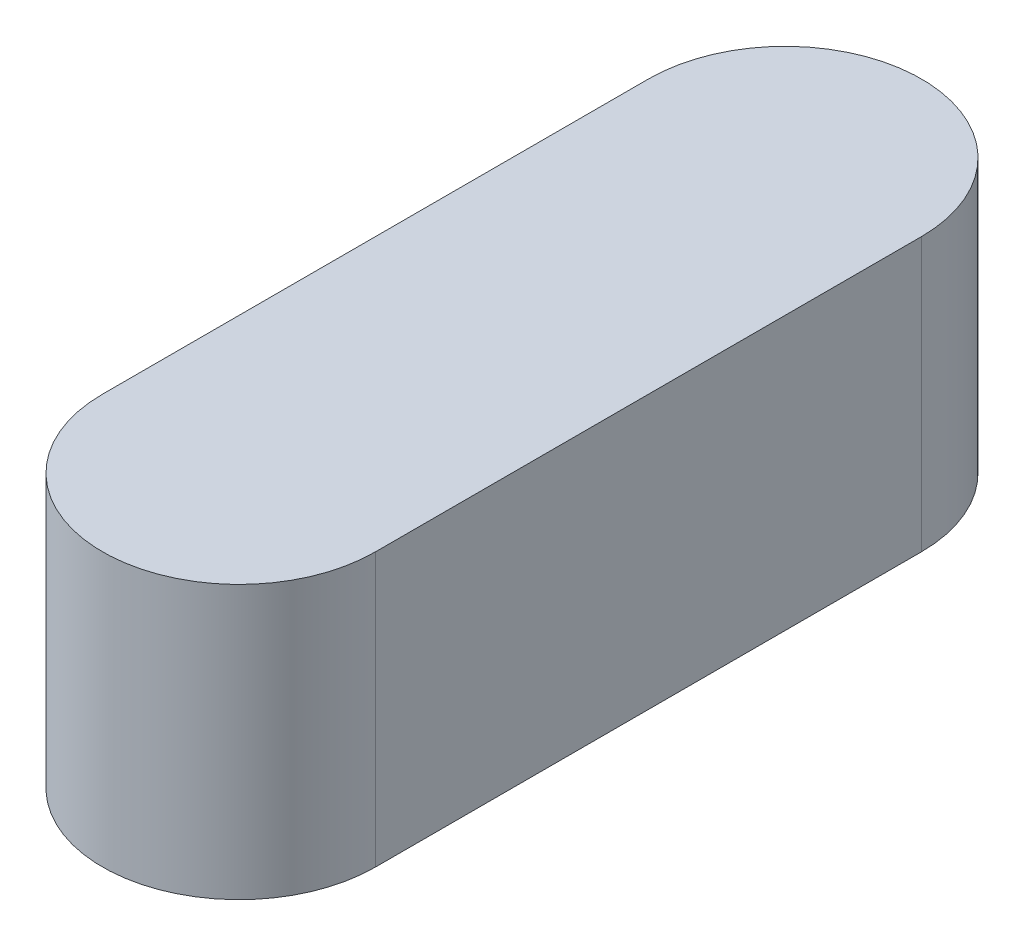
SolidWorks part; units mm, degrees
ref_plane "Plano frontal" through (0, 0, 0) normal (0, 0, 1) x (1, 0, 0)
ref_plane "Plano superior" through (0, 0, 0) normal (0, 1, 0) x (1, 0, 0)
ref_plane "Plano direito" through (0, 0, 0) normal (1, 0, 0) x (0, 0, -1)
sketch "Esboço1" plane through (0, 0, 0) normal (0, 0, 1) x (1, 0, 0)
  line L1 (-2, -2) -> (2, -2)
  line L2 (-2, -2) -> (-2, 2)
  line L3 (-2, 2) -> (2, 2)
  line L4 (2, -2) -> (2, 2)
  line L5 (-2, -2) -> (2, 2) construction
  line L6 (-2, 2) -> (2, -2) construction
  point P0 (0, 0)
  dimension "D1" = 4
  dimension "D2" = 4
extrude "Ressalto-extrusão1" add sketch "Esboço1" along normal blind 12
fillet "Filete1" 2 edges at (-2, 0, 12) (2, 0, 12) type full round first side face at (-2, 0, 6) second side face at (2, 0, 6) middle face at (0, 0, 12)
fillet "Filete2" 2 edges at (2, 0, 0) (-2, 0, 0) type full round first side face at (2, 0, 5) second side face at (-2, 0, 5) middle face at (0, 0, 0)
